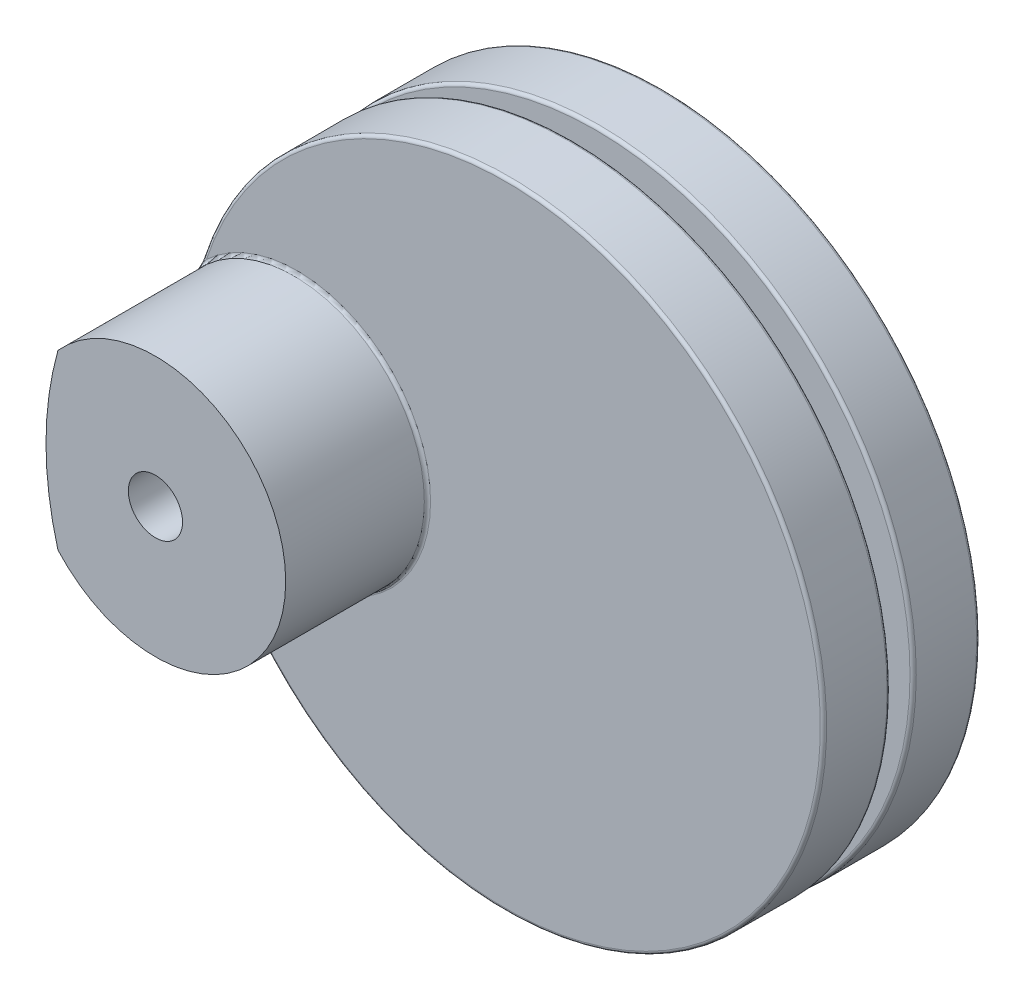
SolidWorks part; units mm, degrees
ref_plane "Front Plane" through (0, 0, 0) normal (0, 0, 1) x (1, 0, 0)
ref_plane "Top Plane" through (0, 0, 0) normal (0, 1, 0) x (1, 0, 0)
ref_plane "Right Plane" through (0, 0, 0) normal (1, 0, 0) x (0, 0, -1)
sketch "Sketch1" plane through (0, 0, 0) normal (0, 0, 1) x (1, 0, 0)
  circle A0 centre (0, 0) radius 30.5
  dimension "D1" = 61
extrude "Boss-Extrude1" add sketch "Sketch1" along normal blind 15
sketch "Sketch2" plane through (0, 0, 15) normal (0, 0, 1) x (1, 0, 0)
  circle A0 centre (-20, 0) radius 12.5
  dimension "D1" = 25
  dimension "D2" = 20
extrude "Boss-Extrude2" add sketch "Sketch2" along normal blind 13.6
sketch "Sketch3" plane through (0, 0, 28.6) normal (0, 0, 1) x (1, 0, 0)
  circle A0 centre (-20, 0) radius 2.6
  dimension "D1" = 5.2
extrude "Cut-Extrude1" cut sketch "Sketch3" against normal through all
sketch "Sketch4" plane through (0, 0, 0) normal (0, 0, -1) x (-1, 0, 0)
  circle A0 centre (20, 0) radius 5
  dimension "D1" = 10
extrude "Cut-Extrude2" cut sketch "Sketch4" against normal blind 6
sketch "Sketch5" plane through (0, 0, 0) normal (0, 1, 0) x (1, 0, 0)
  line L0 (0, 12.6466) -> (0, -38.8355) construction
  line L1 (30.5, -15) -> (30.5, 0) construction
  line L2 (38.5, -8.6) -> (22.5, -8.6)
  line L3 (38.5, -8.6) -> (38.5, -6.4)
  line L4 (38.5, -6.4) -> (22.5, -6.4)
  line L5 (22.5, -8.6) -> (22.5, -6.4)
  line L6 (38.5, -8.6) -> (22.5, -6.4) construction
  line L7 (38.5, -6.4) -> (22.5, -8.6) construction
  point P3 (30.5, -7.5)
  point P10 (30.5, -8.6)
  dimension "D1" = 2.2
  dimension "D2" = 7.5
  dimension "D3" = 8
revolve "Cut-Revolve1" cut sketch "Sketch5" angle 360 about L0
sketch "Sketch6" plane through (0, 0, 15) normal (0, 0, -1) x (-1, 0, 0)
  arc A0 (29.35, -8.2962) -> (29.35, 8.2962) centre (0, 0) ccw
  arc A1 (29.35, -8.2962) -> (29.35, 8.2962) centre (20, 0) ccw
extrude "Cut-Extrude3" cut sketch "Sketch6" against normal through all
fillet "Fillet1" radius 0.3 8 edges at (-29.35, -8.2962, 21.8) (-29.35, 8.2962, 21.8) (30.5, 0, 15) (-7.5, 0, 15) (30.5, 0, 0) (-25, 0, 0) (30.5, 0, 6.4) (-30.5, 0, 8.6)
sketch "Sketch7" plane through (0, 0, 0) normal (0, 0, -1) x (-1, 0, 0)
  line L0 (46.0258, 0) -> (-45.0272, 0) construction
